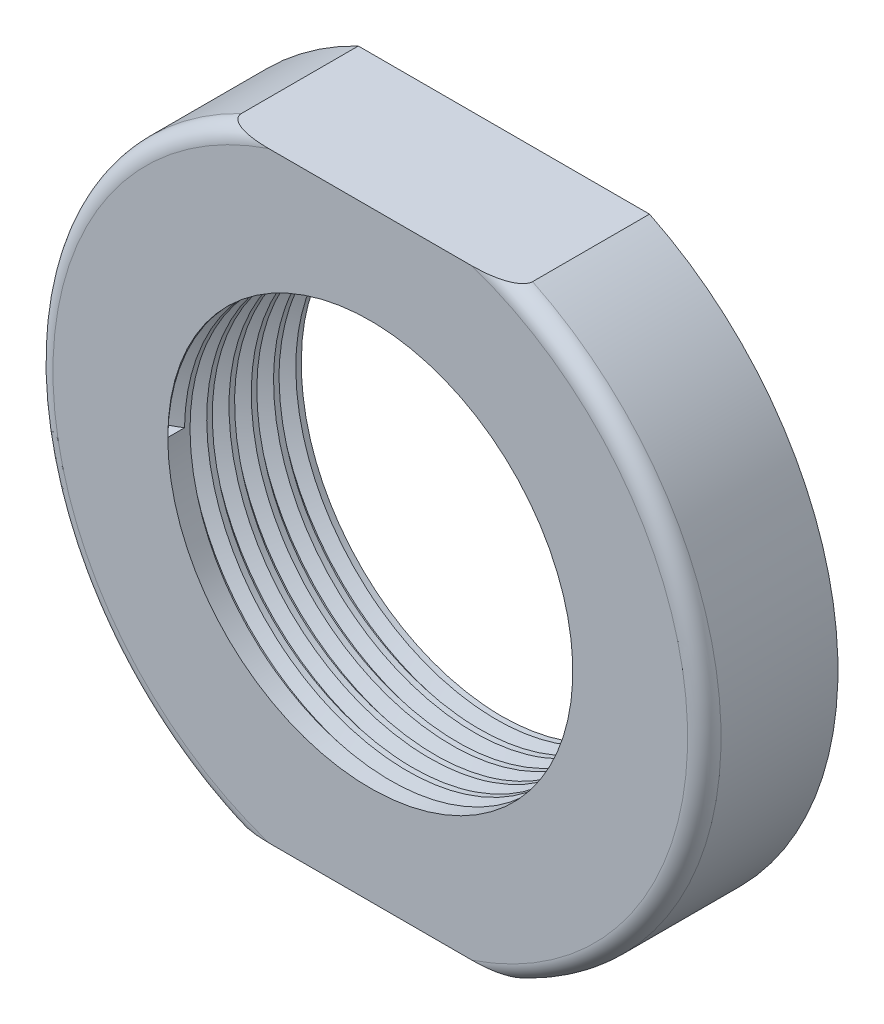
SolidWorks part; units mm, degrees
material "A-1"
ref_plane "Front Plane" through (0, 0, 0) normal (0, 0, 1) x (1, 0, 0)
ref_plane "Top Plane" through (0, 0, 0) normal (0, 1, 0) x (1, 0, 0)
ref_plane "Right Plane" through (0, 0, 0) normal (1, 0, 0) x (0, 0, -1)
sketch "Sketch2" plane through (0, 0, 0) normal (0, 0, 1) x (1, 0, 0)
  line L0 (-13.8395, 28.575) -> (13.8395, 28.575)
  line L1 (-42.1917, 0) -> (49957.8083, 0) construction
  line L2 (-13.8395, -28.575) -> (13.8395, -28.575)
  arc A0 (-13.8395, 28.575) -> (-13.8395, -28.575) centre (0, 0) ccw
  arc A1 (13.8395, -28.575) -> (13.8395, 28.575) centre (0, 0) ccw
  dimension "D3" = 31.75
  dimension "D2" = 57.15
extrude "Boss-Extrude1" add sketch "Sketch2" against normal blind 12.7
sketch "Sketch5" plane through (0, 0, 0) normal (0, 0, 1) x (1, 0, 0)
  circle A0 centre (0, 0) radius 19.2484
  dimension "D1" = 38.4969
extrude "Cut-Extrude1" cut sketch "Sketch5" against normal through all
fillet "Fillet1" radius 1.5875 2 edges at (-31.75, 0, 0) (31.75, 0, 0)
thread "Thread1" pitch 2.1167 method cut profile "Thread Profile2" start angle 0, offset 0, length 38.1, pitch 2.1167, diameter 38.4969
ref_plane "Plane2" through (-19.2484, 0, 0) normal (0, -1, 0) x (-1, 0, 0)
sketch "Thread Profile2" plane through (-19.2484, 0, 0) normal (0, -1, 0) x (-1, 0, 0)
  line L0 (0, 0) -> (0, 2.1167) construction
  line L1 (0, 0) -> (1.1457, 0.6615)
  line L2 (1.1457, 0.6615) -> (1.1457, 0.926)
  line L3 (1.1457, 0.926) -> (0, 1.5875)
  line L4 (1.1457, 0.7937) -> (0, 0.7937) construction
  line L11 (0, 0) -> (0, 1.5875)
  point P2 (0, 0)
  dimension "Pitch" = 2.1167
  dimension "Profile_Angle" = 60
  dimension "Profile_Land" = 0.2646
  dimension "Profile_Height" = 1.1457
